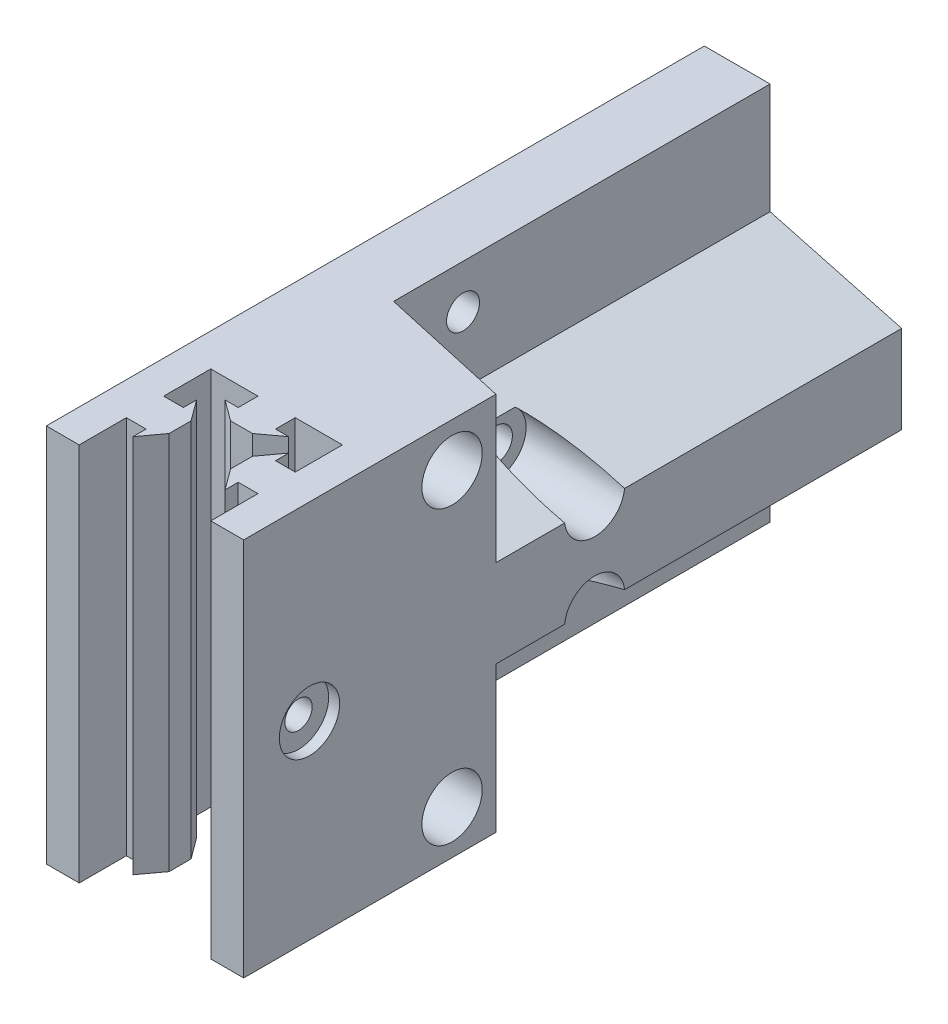
SolidWorks part; units mm, degrees
ref_plane "Plan de face" through (0, 0, 0) normal (0, 0, 1) x (1, 0, 0)
ref_plane "Plan de dessus" through (0, 0, 0) normal (0, 1, 0) x (1, 0, 0)
ref_plane "Plan de droite" through (0, 0, 0) normal (1, 0, 0) x (0, 0, -1)
ref_plane "Plan milieu" through (0, 0, -54) normal (0, 0, 1) x (1, 0, 0)
ref_axis "Axe1" through (0, 17.691, 0) along (0, -1, 0)
ref_axis "Axe2" through (23.7847, 0, 0) along (-1, 0, 0)
ref_axis "Axe3" through (0, 0, -21.7718) along (0, 0, 1)
sketch "Esquisse8" plane through (0, 0, 0) normal (0, 1, 0) x (1, 0, 0)
  line L0 (-6, 1.7) -> (-4.2, 1.7)
  line L1 (0, -16.9042) -> (0, 16.9042) construction
  line L2 (-4.2, 1.7) -> (-4.2, 2.9)
  line L3 (-4.2, 2.9) -> (-2.8, 1)
  line L4 (-2.8, 1) -> (-2.8, -1)
  line L5 (-2.8, -1) -> (-4.2, -2.9)
  line L6 (-4.2, -2.9) -> (-4.2, -1.7)
  line L7 (-4.2, -1.7) -> (-6, -1.7)
  line L8 (-6, -1.7) -> (-6, -9)
  line L9 (-6, -9) -> (-9, -9)
  line L10 (-9, -9) -> (-9, 9)
  line L11 (-9, 9) -> (-6, 9)
  line L12 (-6, 9) -> (-6, 1.7)
  line L16 (23.7847, 0) -> (-17.9556, 0) construction
  point P14 (-2.8, 0)
  dimension "D1" = 1.8
  dimension "D2" = 3.2
  dimension "D3" = 18
  dimension "D4" = 2
  dimension "D5" = 1.2
  dimension "D7" = 3
  dimension "D8" = 3.4
  dimension "D9" = 6
extrude "Boss.-Extru.6" add sketch "Esquisse8" along normal mid plane 34.6 separate body
pattern_circular "Répétition circulaire3" count 3 every 90 about axis through (0, 17.691, 0) along (0, -1, 0) of bodies 117
sketch "Esquisse9" plane through (0, 17.3, 0) normal (0, 1, 0) x (1, 0, 0)
  line L0 (9, -9) -> (9, 9) construction
  line L1 (-9, -9) -> (9, -9)
  line L2 (-9, -9) -> (-9, -6)
  line L3 (-9, -6) -> (9, -6)
  line L4 (9, -9) -> (9, -6)
  dimension "D1" = 3
extrude "Enlèv. mat.-Extru.1" cut sketch "Esquisse9" against normal through all
sketch "Esquisse10" plane through (0, 0, -9) normal (0, 0, -1) x (-1, 0, 0)
  line L0 (6, -17.3) -> (9, -17.3) construction
  line L1 (9, 17.3) -> (3, 17.3)
  line L2 (9, 17.3) -> (9, -17.3)
  line L3 (9, -17.3) -> (3, -17.3)
  line L4 (3, 17.3) -> (3, -17.3)
  line L5 (-9, -17.3) -> (9, -17.3) construction
  dimension "D1" = 6
extrude "Boss.-Extru.7" add sketch "Esquisse10" along normal blind 45
sketch "Esquisse13" plane through (0, -17.3, 0) normal (0, -1, 0) x (-1, 0, 0)
  line L0 (9, 21) -> (-9, 17)
  line L1 (9, 54) -> (9, -6) construction
  line L2 (9, 21) -> (9, 9)
  line L3 (9, 9) -> (-9, 9)
  line L4 (-9, 6) -> (-9, 9) construction
  line L5 (-9, 17) -> (-9, 9)
  line L6 (9, 54) -> (9, -6) construction
  dimension "D1" = 12
  dimension "D2" = 8
extrude "Boss.-Extru.8" add sketch "Esquisse13" against normal up to surface (34.6 mm away) up to face at (-1.9333, 17.3, -7.6208)
sketch "Esquisse17" plane through (-3, 0, 0) normal (1, 0, 0) x (0, 0, -1)
  line L1 (17, -4) -> (54, -4)
  line L2 (17, -4) -> (17, 4)
  line L3 (17, 4) -> (54, 4)
  line L4 (54, -4) -> (54, 4)
  line L5 (54, 17.3) -> (54, -17.3) construction
  line L6 (17, 17.3) -> (17, -17.3) construction
  point P4 (54, 0)
  point P5 (54, 0)
  dimension "D1" = 8
extrude "Boss.-Extru.9" add sketch "Esquisse17" along normal up to vertex (12 mm away) up to point (9, 17.3, -17)
sketch "Esquisse18" plane through (0, 0, -54) normal (0, 0, -1) x (-1, 0, 0)
  line L0 (3, 7.2154) -> (-9, 4)
  line L1 (3, 17.3) -> (3, 4) construction
  line L2 (-9, 4) -> (-9, -4)
  line L3 (-9, -4) -> (3, -7.2154)
  line L4 (3, -4) -> (3, -17.3) construction
  line L5 (3, -7.2154) -> (3, 7.2154)
  line L6 (-9, 4) -> (3, 4) construction
  dimension "D1" = 15
extrude "Boss.-Extru.10" add sketch "Esquisse18" against normal up to surface (37 mm away) up to face at (3, 10.65, -18.3333)
sketch "Esquisse11" plane through (-9, 0, 0) normal (-1, 0, 0) x (0, 0, 1)
  line L0 (-54, -17.3) -> (-54, 17.3) construction
  line L1 (-54, -17.3) -> (6, -17.3) construction
  circle A0 centre (-26, -13.3) radius 1.5
  circle A1 centre (-26, -4.3) radius 1.5
  circle A2 centre (-13, -13.3) radius 1.5
  dimension "D1" = 3
  dimension "D4" = 13
  dimension "D5" = 13
  dimension "D2" = 28
  dimension "D3" = 4
extrude "Enlèv. mat.-Extru.2" cut sketch "Esquisse11" against normal mid plane 50
sketch "Esquisse15" plane through (9, 0, 0) normal (1, 0, 0) x (0, 0, -1)
  line L0 (-6, -17.3) -> (-6, 17.3) construction
  line L2 (0, 17.691) -> (0, -16.1174) construction
  circle A0 centre (0, 0) radius 1.25
  point P2 (-6, 0)
  dimension "D1" = 2.5
extrude "Enlèv. mat.-Extru.3" cut sketch "Esquisse15" against normal up to next
sketch "Esquisse19" plane through (9, 0, 0) normal (1, 0, 0) x (0, 0, -1)
  circle A0 centre (0, 0) radius 2.75
  circle A1 centre (0, 0) radius 1.25 construction
  dimension "D1" = 5.5
extrude "Enlèv. mat.-Extru.5" cut sketch "Esquisse19" against normal blind 1
sketch "Esquisse16" plane through (0, 0, 0) normal (1, 0, 0) x (0, 0, -1)
  circle A0 centre (13, -13.3) radius 2.75
  circle A1 centre (13, -13.3) radius 1.5 construction
  circle A2 centre (26, -4.3) radius 2.75
  circle A3 centre (26, -4.3) radius 1.5 construction
  dimension "D1" = 5.5
extrude "Enlèv. mat.-Extru.4" cut sketch "Esquisse16" along normal up to next
mirror "Symétrie2" about plane through (0, 0, 0) normal (0, 1, 0) of "Enlèv. mat.-Extru.4", "Enlèv. mat.-Extru.2"
